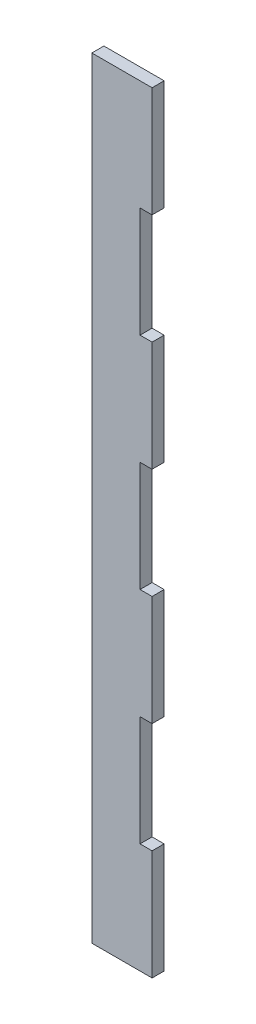
SolidWorks part; units mm, degrees
ref_plane "Front Plane" through (0, 0, 0) normal (0, 0, 1) x (1, 0, 0)
ref_plane "Top Plane" through (0, 0, 0) normal (0, 1, 0) x (1, 0, 0)
ref_plane "Right Plane" through (0, 0, 0) normal (1, 0, 0) x (0, 0, -1)
sketch "Sketch1" plane through (0, 0, 0) normal (0, 0, 1) x (1, 0, 0)
  line L0 (0, 101.6) -> (0, -101.6) construction
  line L1 (-6.35, 101.6) -> (6.35, 101.6)
  line L2 (-6.35, 101.6) -> (-6.35, -101.6)
  line L3 (-6.35, -101.6) -> (6.35, -101.6)
  line L4 (6.35, 101.6) -> (6.35, -101.6)
  line L5 (6.35, 72.5714) -> (6.35, 43.5429)
  line L6 (6.35, 101.6) -> (9.525, 101.6)
  line L7 (6.35, 101.6) -> (6.35, 72.5714)
  line L8 (6.35, 72.5714) -> (9.525, 72.5714)
  line L9 (9.525, 101.6) -> (9.525, 72.5714)
  line L10 (6.35, 72.5714) -> (9.525, 72.5714)
  line L11 (9.525, 72.5714) -> (9.525, 43.5429)
  line L12 (6.35, 43.5429) -> (9.525, 43.5429)
  line L13 (6.35, 43.5429) -> (6.35, 14.5143)
  line L14 (6.35, 43.5429) -> (9.525, 43.5429)
  line L15 (9.525, 43.5429) -> (9.525, 14.5143)
  line L16 (6.35, 14.5143) -> (9.525, 14.5143)
  line L17 (6.35, 14.5143) -> (6.35, -14.5143)
  line L18 (6.35, 14.5143) -> (9.525, 14.5143)
  line L19 (9.525, 14.5143) -> (9.525, -14.5143)
  line L20 (6.35, -14.5143) -> (9.525, -14.5143)
  line L21 (6.35, -14.5143) -> (6.35, -43.5429)
  line L22 (6.35, -14.5143) -> (9.525, -14.5143)
  line L23 (9.525, -14.5143) -> (9.525, -43.5429)
  line L24 (6.35, -43.5429) -> (9.525, -43.5429)
  line L25 (6.35, -43.5429) -> (6.35, -72.5714)
  line L26 (6.35, -43.5429) -> (9.525, -43.5429)
  line L27 (9.525, -43.5429) -> (9.525, -72.5714)
  line L28 (6.35, -72.5714) -> (9.525, -72.5714)
  line L29 (6.35, -72.5714) -> (6.35, -101.6)
  line L30 (6.35, -72.5714) -> (9.525, -72.5714)
  line L31 (9.525, -72.5714) -> (9.525, -101.6)
  line L32 (6.35, -101.6) -> (9.525, -101.6)
  point P6 (0, 0)
  dimension "D2" = 12.7
  dimension "D1" = 203.2
  dimension "D3" = 29.0286
  dimension "D4" = 3.175
  dimension "D5" = 7
extrude "Boss-Extrude1" add sketch "Sketch1" along normal blind 3.175 contours L0 L1 L2 L3 | L1 L0 L3 L4 | L9 L6 L4 L8 | L4 L16 L15 L12 | L4 L24 L23 L20 | L4 L32 L31 L28 region at (3.175, 0, 0) region at (-3.175, 0, 0) region at (7.9375, 87.0857, 0) region at (7.9375, -87.0857, 0) region at (7.9375, 29.0286, 0) region at (7.9375, -29.0286, 0)
equation "\"Height\"= 12in"
equation "\"Depth\"= 7in"
equation "\"WallThickness\"= 0.125in"
equation "\"FloorThickness\"= 0.25in"
equation "\"Width\" = 30in"
equation "\"D1@Boss-Extrude1\"=\"WallThickness\""
equation "\"D3@Sketch1\"=\"D1@Sketch1\"/\"D5@Sketch1\""
equation "\"D4@Sketch1\"=\"WallThickness\""
